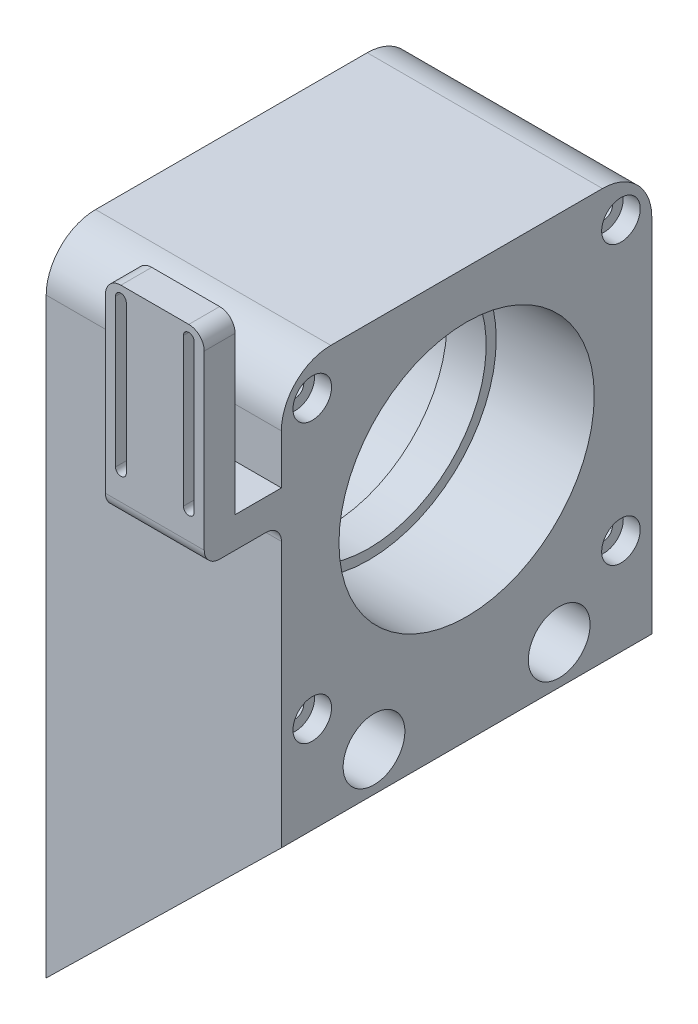
SolidWorks part; units mm, degrees
ref_plane "Front Plane" through (0, 0, 0) normal (0, 0, 1) x (1, 0, 0)
ref_plane "Top Plane" through (0, 0, 0) normal (0, 1, 0) x (1, 0, 0)
ref_plane "Right Plane" through (0, 0, 0) normal (1, 0, 0) x (0, 0, -1)
sketch "Sketch1" plane through (0, 0, 0) normal (0, 0, 1) x (1, 0, 0)
  line L0 (381, 457.2) -> (457.2, 457.2)
  line L1 (457.2, 457.2) -> (457.2, 431.8)
  line L2 (381, 457.2) -> (381, 357.2)
  line L5 (381, 357.2) -> (457.2, 431.8)
  dimension "D1" = 76.2
  dimension "D2" = 100
extrude "Boss-Extrude1" add sketch "Sketch1" along normal blind 120
sketch "Sketch3" plane through (457.2, 0, 0) normal (1, 0, 0) x (0, 0, -1)
  line L1 (-120, 431.8) -> (0, 431.8)
  line L2 (-120, 431.8) -> (-120, 357.2)
  line L3 (-120, 357.2) -> (0, 357.2)
  line L4 (0, 431.8) -> (0, 357.2)
  circle A0 centre (-90, 394.5) radius 4.25
  circle A1 centre (-30, 394.5) radius 4.25
  circle A2 centre (-90, 444.5) radius 4.25
  circle A3 centre (-30, 444.5) radius 4.25
  dimension "D1" = 30
  dimension "D2" = 30
  dimension "D3" = 37.3
  dimension "D4" = 37.3
extrude "Cut-Extrude1" cut sketch "Sketch3" against normal blind 120 contours A1 | A0
sketch "Sketch5" plane through (457.2, 0, 0) normal (1, 0, 0) x (0, 0, -1)
  circle A0 centre (-90, 394.5) radius 10
  circle A1 centre (-30, 394.5) radius 10
  circle A2 centre (-90, 444.5) radius 10
  circle A3 centre (-30, 444.5) radius 10
extrude "Cut-Extrude2" cut sketch "Sketch5" against normal blind 53
sketch "Sketch6" plane through (457.2, 0, 0) normal (1, 0, 0) x (0, 0, -1)
  circle A0 centre (-90, 444.5) radius 4.25
  circle A1 centre (-30, 444.5) radius 4.25
extrude "Cut-Extrude3" cut sketch "Sketch6" against normal blind 103
sketch "Sketch7" plane through (0, 457.2, 0) normal (0, 1, 0) x (1, 0, 0)
  line L1 (381, 0) -> (457.2, 0)
  line L2 (381, 0) -> (381, -120)
  line L3 (381, -120) -> (457.2, -120)
  line L4 (457.2, 0) -> (457.2, -120)
extrude "Boss-Extrude2" add sketch "Sketch7" along normal blind 101.6
sketch "Sketch8" plane through (381, 0, 0) normal (-1, 0, 0) x (0, 0, 1)
  line L0 (120, 457.2) -> (0, 457.2)
  line L1 (120, 558.8) -> (120, 357.2) construction
  line L2 (0, 558.8) -> (0, 357.2) construction
  line L3 (0, 558.8) -> (120, 558.8) construction
  circle A0 centre (60, 508) radius 41.35
  dimension "D1" = 101.6
  dimension "D2" = 50.8
extrude "Cut-Extrude4" cut sketch "Sketch8" against normal blind 31.75 contours A0 region at (381, 508, 60)
sketch "Sketch9" plane through (457.2, 0, 0) normal (1, 0, 0) x (0, 0, -1)
  line L0 (-120, 558.8) -> (0, 558.8) construction
  line L1 (-120, 431.8) -> (-120, 558.8) construction
  circle A0 centre (-60, 508) radius 41.35
  dimension "D1" = 50.8
  dimension "D2" = 60
extrude "Cut-Extrude5" cut sketch "Sketch9" against normal blind 31.75
sketch "Sketch10" plane through (457.2, 0, 0) normal (1, 0, 0) x (0, 0, -1)
  circle A0 centre (-60, 508) radius 38.1
extrude "Cut-Extrude6" cut sketch "Sketch10" against normal blind 76.2
sketch "Sketch13" plane through (0, 558.8, 0) normal (0, 1, 0) x (1, 0, 0)
  line L1 (381, 0) -> (457.2, 0)
  line L2 (381, 0) -> (381, -120)
  line L3 (381, -120) -> (457.2, -120)
  line L4 (457.2, 0) -> (457.2, -120)
extrude "Boss-Extrude3" add sketch "Sketch13" along normal blind 6
sketch "Sketch11" plane through (457.2, 0, 0) normal (1, 0, 0) x (0, 0, -1)
  line L0 (-120, 431.8) -> (-120, 564.8) construction
  line L1 (-110, 553) -> (-10, 553)
  line L2 (-110, 553) -> (-110, 463)
  line L3 (-110, 463) -> (-10, 463)
  line L4 (-10, 553) -> (-10, 463)
  line L5 (0, 431.8) -> (0, 564.8) construction
  circle A0 centre (-60, 508) radius 5.3331
  circle A1 centre (-110, 553) radius 2.75
  circle A2 centre (-10, 553) radius 2.75
  circle A3 centre (-10, 463) radius 2.75
  circle A4 centre (-110, 463) radius 2.75
  dimension "D1" = 10
  dimension "D2" = 10
  dimension "D3" = 45
  dimension "D4" = 90
extrude "Cut-Extrude7" cut sketch "Sketch11" against normal blind 84.4 contours L1 A1 L2 | L2 A1 L1 | L4 A2 L1 | L1 A2 L4 | L3 A3 L4 | L4 A3 L3 | L2 A4 L3 | L3 A4 L2 region at (457.2, 553.389, 110.389) region at (457.2, 551.8329, 108.8329) region at (457.2, 553.389, 9.611) region at (457.2, 551.8329, 11.1671) region at (457.2, 464.1671, 108.8329) region at (457.2, 462.611, 110.389) region at (457.2, 462.611, 9.611) region at (457.2, 464.1671, 11.1671)
sketch "Sketch12" plane through (457.2, 0, 0) normal (1, 0, 0) x (0, 0, -1)
  circle A0 centre (-110, 553) radius 6.25
  circle A1 centre (-10, 553) radius 6.25
  circle A2 centre (-10, 463) radius 6.25
  circle A3 centre (-110, 463) radius 6.25
extrude "Cut-Extrude8" cut sketch "Sketch12" against normal blind 5.5
fillet "Fillet1" radius 16 2 edges at (419.1, 564.8, 0) (419.1, 564.8, 120)
sketch "Sketch18" plane through (0, 0, 120) normal (0, 0, 1) x (1, 0, 0)
  line L0 (457.2, 431.8) -> (457.2, 548.8) construction
  line L1 (457.2, 522.8) -> (425.2, 522.8)
  line L2 (457.2, 522.8) -> (457.2, 532.8)
  line L3 (457.2, 532.8) -> (425.2, 532.8)
  line L4 (425.2, 522.8) -> (425.2, 532.8)
  line L6 (381, 564.8) -> (457.2, 564.8) construction
  dimension "D1" = 32
  dimension "D2" = 32
  dimension "D3" = 10
extrude "Boss-Extrude6" add sketch "Sketch18" along normal blind 15
sketch "Sketch20" plane through (0, 0, 135) normal (0, 0, 1) x (1, 0, 0)
  line L0 (431.95, 584.6825) -> (431.95, 536.8)
  line L2 (425.2, 532.8) -> (425.2, 588.6825)
  line L3 (425.2, 588.6825) -> (457.2, 588.6825)
  line L4 (457.2, 536.6825) -> (457.2, 588.6825)
  line L5 (428.45, 584.6825) -> (428.45, 536.8)
  line L6 (450.45, 584.6825) -> (450.45, 536.8)
  line L7 (450.45, 584.6825) -> (450.45, 536.8)
  line L8 (425.2, 532.8) -> (425.2, 522.8)
  line L9 (425.2, 522.8) -> (457.2, 522.8)
  line L10 (457.2, 522.8) -> (457.2, 536.6825)
  line L11 (453.95, 584.6825) -> (453.95, 536.8)
  circle A0 centre (430.2, 584.6825) radius 1.75
  circle A1 centre (452.2, 584.6825) radius 1.75
  circle A2 centre (452.2, 536.8) radius 1.75
  circle A3 centre (430.2, 536.8) radius 1.75
  line M6 (457.2, 522.8) -> (457.2, 532.8)
  line M7 (457.2, 532.8) -> (425.2, 532.8)
  line M8 (425.2, 532.8) -> (425.2, 522.8)
  line M9 (425.2, 522.8) -> (457.2, 522.8)
  dimension "D1" = 22
  dimension "D2" = 22
  dimension "D3" = 5
  dimension "D4" = 52
  dimension "D5" = 4
  dimension "D6" = 5
  dimension "D7" = 4
extrude "Boss-Extrude7" add sketch "Sketch20" along normal blind 10 contours L4 L3 L2 A3 L5 A0 L0 A2 L6 A1 L7 M7 | M9 M6 M7 M8 region at (441.2, 527.8, 135) region at (441.2, 560.7413, 135)
fillet "Fillet3" radius 5 4 edges at (441.2, 522.8, 145) (425.2, 588.6825, 140) (457.2, 588.6825, 140) (441.2, 522.8, 120)
